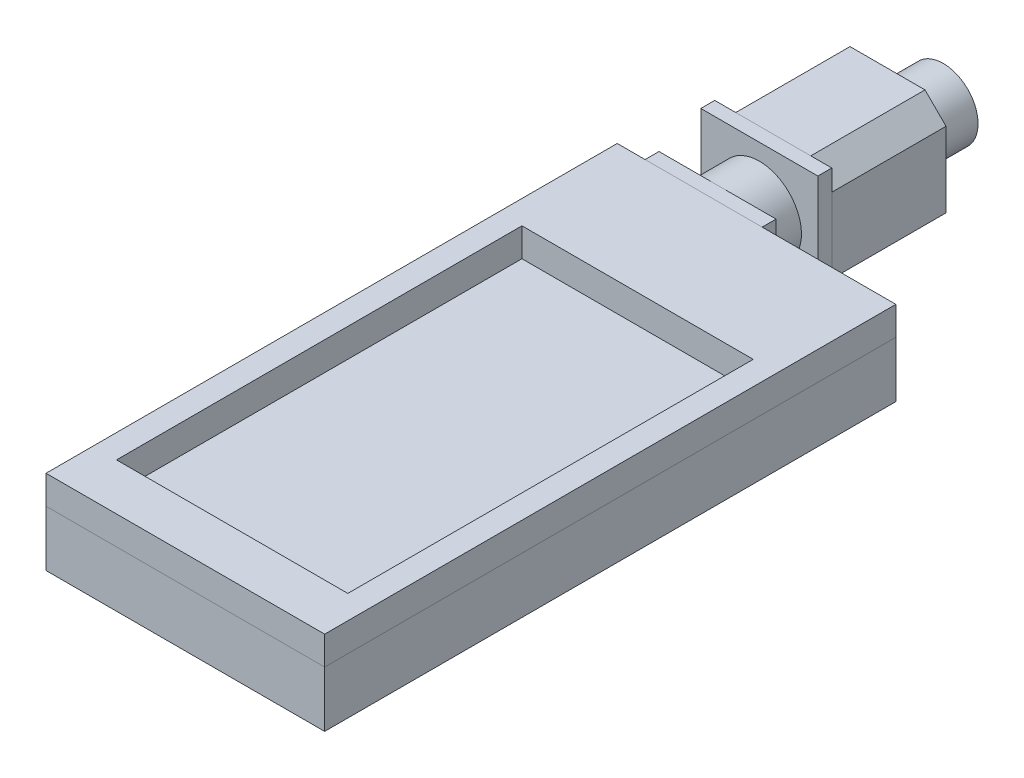
SolidWorks part; units mm, degrees
ref_plane "Front Plane" through (0, 0, 0) normal (0, 0, 1) x (1, 0, 0)
ref_plane "Top Plane" through (0, 0, 0) normal (0, 1, 0) x (1, 0, 0)
ref_plane "Right Plane" through (0, 0, 0) normal (1, 0, 0) x (0, 0, -1)
sketch "Sketch1" plane through (0, 0, 0) normal (0, 1, 0) x (1, 0, 0)
  line L0 (0, 59.81) -> (0, -85.69) construction
  line L1 (-50, 102.5) -> (50, 102.5)
  line L2 (-50, 102.5) -> (-50, -102.5)
  line L3 (-50, -102.5) -> (50, -102.5)
  line L4 (50, 102.5) -> (50, -102.5)
  line L5 (-50, 102.5) -> (50, -102.5) construction
  line L6 (-50, -102.5) -> (50, 102.5) construction
  line L7 (-41.5, 59.81) -> (41.5, 59.81)
  line L8 (-41.5, 59.81) -> (-41.5, -85.69)
  line L9 (-41.5, -85.69) -> (41.5, -85.69)
  line L10 (41.5, 59.81) -> (41.5, -85.69)
  point P0 (0, 0)
  dimension "D1" = 100
  dimension "D2" = 205
  dimension "D3" = 83
  dimension "D4" = 16.81
  dimension "D5" = 145.5
extrude "Boss-Extrude1" add sketch "Sketch1" along normal blind 10.24
sketch "Sketch2" plane through (0, 0, 0) normal (0, -1, 0) x (1, 0, 0)
  line L4 (50, -102.5) -> (50, 102.5)
  line L5 (50, 102.5) -> (-50, 102.5)
  line L6 (-50, 102.5) -> (-50, -102.5)
  line L7 (-50, -102.5) -> (50, -102.5)
  line L8 (50, -102.5) -> (50, 102.5)
  line L9 (50, 102.5) -> (-50, 102.5)
  line L10 (-50, 102.5) -> (-50, -102.5)
  line L11 (-50, -102.5) -> (50, -102.5)
  dimension "D1" = 0
extrude "Boss-Extrude2" add sketch "Sketch2" along normal blind 20 separate body
sketch "Sketch6" plane through (0, 0, -102.5) normal (0, 0, -1) x (-1, 0, 0)
  line L0 (50, -20) -> (-50, -20) construction
  line L1 (40, -20) -> (-2, -20)
  line L2 (40, -20) -> (40, 10.24)
  line L3 (40, 10.24) -> (-2, 10.24)
  line L4 (-2, -20) -> (-2, 10.24)
  line L5 (-50, 10.24) -> (50, 10.24) construction
  line L6 (50, -20) -> (50, 0) construction
  dimension "D1" = 10
  dimension "D2" = 42
extrude "Boss-Extrude4" add sketch "Sketch6" along normal blind 5 separate body
sketch "Sketch7" plane through (0, 0, -107.5) normal (0, 0, -1) x (-1, 0, 0)
  line L4 (19, -20) -> (19, 10.24) construction
  line L5 (-2, -20) -> (40, -20) construction
  line L6 (40, 10.24) -> (-2, 10.24) construction
  circle A0 centre (19, -4.88) radius 15.12
  dimension "D1" = 30.24
extrude "Boss-Extrude5" add sketch "Sketch7" along normal blind 15
sketch "Sketch8" plane through (0, 0, -122.5) normal (0, 0, -1) x (-1, 0, 0)
  line L1 (40, -25.88) -> (-2, -25.88)
  line L2 (40, -25.88) -> (40, 16.12)
  line L3 (40, 16.12) -> (-2, 16.12)
  line L4 (-2, -25.88) -> (-2, 16.12)
  line L5 (40, -25.88) -> (-2, 16.12) construction
  line L6 (40, 16.12) -> (-2, -25.88) construction
  point P0 (19, -4.88)
  dimension "D1" = 42
  dimension "D2" = 42
extrude "Boss-Extrude6" add sketch "Sketch8" along normal blind 5
sketch "Sketch9" plane through (0, 0, -127.5) normal (0, 0, -1) x (-1, 0, 0)
  line L0 (40, -18.3403) -> (32.4603, -25.88)
  line L1 (40, -25.88) -> (40, 16.12) construction
  line L2 (-2, -25.88) -> (40, -25.88) construction
  line L3 (32.4603, -25.88) -> (5.5397, -25.88)
  line L4 (40, -18.3403) -> (40, 8.5803)
  line L5 (19, -25.88) -> (19, 16.12) construction
  line L6 (40, 16.12) -> (-2, 16.12) construction
  line L7 (40, -4.88) -> (-2, -4.88) construction
  line L8 (-2, 16.12) -> (-2, -25.88) construction
  line L9 (32.4603, 16.12) -> (5.5397, 16.12)
  line L10 (40, 8.5803) -> (32.4603, 16.12)
  line L11 (-2, 8.5803) -> (5.5397, 16.12)
  line L12 (-2, -18.3403) -> (-2, 8.5803)
  line L13 (-2, -18.3403) -> (5.5397, -25.88)
  dimension "D1" = 45
extrude "Boss-Extrude7" add sketch "Sketch9" along normal blind 41 separate body
sketch "Sketch10" plane through (0, 0, -168.5) normal (0, 0, -1) x (-1, 0, 0)
  line L0 (19, -25.88) -> (19, 16.12) construction
  line L1 (5.5397, -25.88) -> (32.4603, -25.88) construction
  line L2 (32.4603, 16.12) -> (5.5397, 16.12) construction
  circle A0 centre (19, -4.88) radius 12.5
  dimension "D1" = 25
extrude "Boss-Extrude8" add sketch "Sketch10" along normal blind 20 separate body
sketch "Sketch11" plane through (0, 0, -59.81) normal (0, 0, 1) x (1, 0, 0)
  line L0 (-41.5, 5.12) -> (41.5, 5.12) construction
  line L1 (-41.5, 10.24) -> (-41.5, 0) construction
  line L2 (41.5, 10.24) -> (41.5, 0) construction
  circle A0 centre (0, 5.12) radius 2.4401
extrude "Cut-Extrude1" [suppressed] cut sketch "Sketch11" against normal blind 20 and the other way blind 147
sketch "Sketch12" plane through (0, -20, 0) normal (0, -1, 0) x (1, 0, 0)
  line L0 (50, 0) -> (-50, 0) construction
  line L1 (50, -102.5) -> (50, 102.5) construction
  line L2 (-50, 102.5) -> (-50, -102.5) construction
  line L3 (0, -102.5) -> (0, 102.5) construction
  line L4 (-50, -102.5) -> (50, -102.5) construction
  line L5 (50, 102.5) -> (-50, 102.5) construction
  circle A0 centre (25, 77.5) radius 3.05
  circle A1 centre (25, -70.5) radius 3.05
  circle A2 centre (-25, -70.5) radius 3.05
  circle A3 centre (-25, 77.5) radius 3.05
  dimension "D1" = 6.1
  dimension "D2" = 25
  dimension "D3" = 25
  dimension "D4" = 148
extrude "Cut-Extrude2" cut sketch "Sketch12" against normal blind 16
